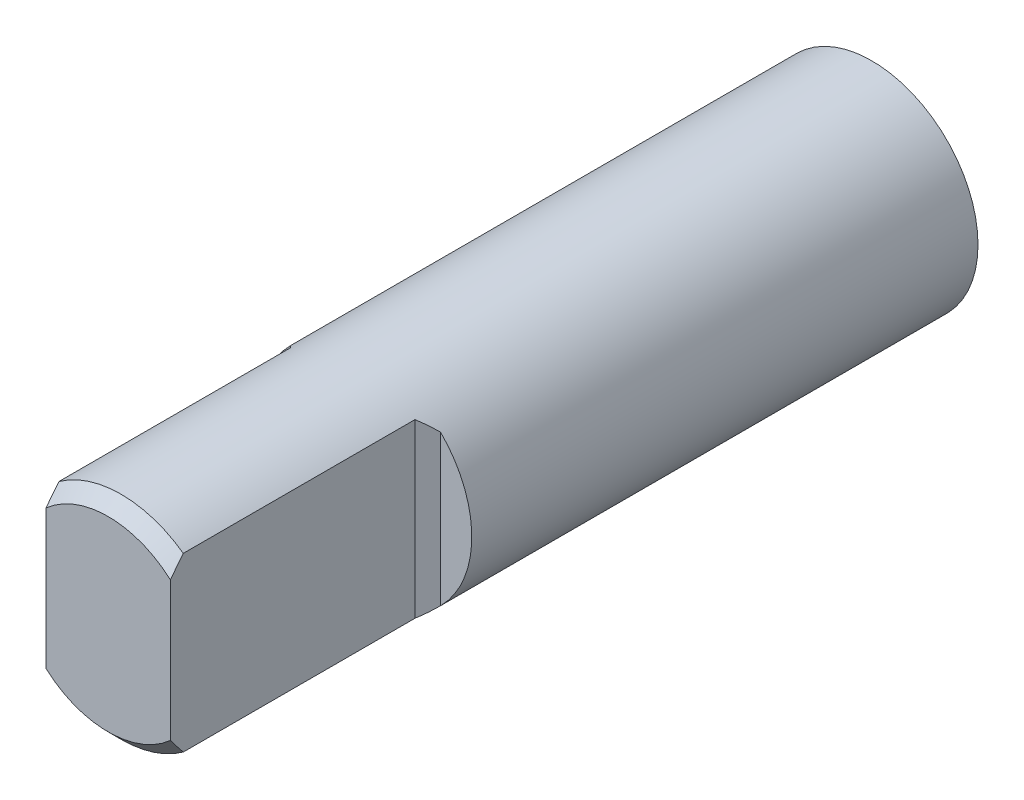
SolidWorks part; units mm, degrees
material "Латунь"
ref_plane "Front Plane" through (0, 0, 0) normal (0, 0, 1) x (1, 0, 0)
ref_plane "Top Plane" through (0, 0, 0) normal (0, 1, 0) x (1, 0, 0)
ref_plane "Right Plane" through (0, 0, 0) normal (1, 0, 0) x (0, 0, -1)
sketch "Sketch1" plane through (0, 0, 0) normal (0, 0, 1) x (1, 0, 0)
  circle A0 centre (0, 0) radius 2.475
  dimension "D1" = 4.95
extrude "Extrude1" add sketch "Sketch1" along normal blind 17.8
sketch "Sketch2" plane through (0, 0, 17.8) normal (0, 0, 1) x (1, 0, 0)
  line L1 (-1.45, 3.5) -> (1.45, 3.5)
  line L2 (-1.45, 3.5) -> (-1.45, -3.5)
  line L3 (-1.45, -3.5) -> (1.45, -3.5)
  line L4 (1.45, 3.5) -> (1.45, -3.5)
  line L5 (-1.45, 3.5) -> (1.45, -3.5) construction
  line L6 (-1.45, -3.5) -> (1.45, 3.5) construction
  point P0 (0, 0)
  dimension "D1" = 7
  dimension "D2" = 2.9
extrude "Extrude2" cut sketch "Sketch2" against normal blind 6 flip side to cut
chamfer "Chamfer1" distance 0.3 angle 45 2 edges at (0, -2.475, 17.8) (0, 2.475, 17.8)
ref_axis "Axis1" through (0, 0, 17.5) along (0, 0, -1)
chamfer "Chamfer2" distance 0.3 angle 45 2 edges at (-1.45, 0, 11.8) (1.45, 0, 11.8)
